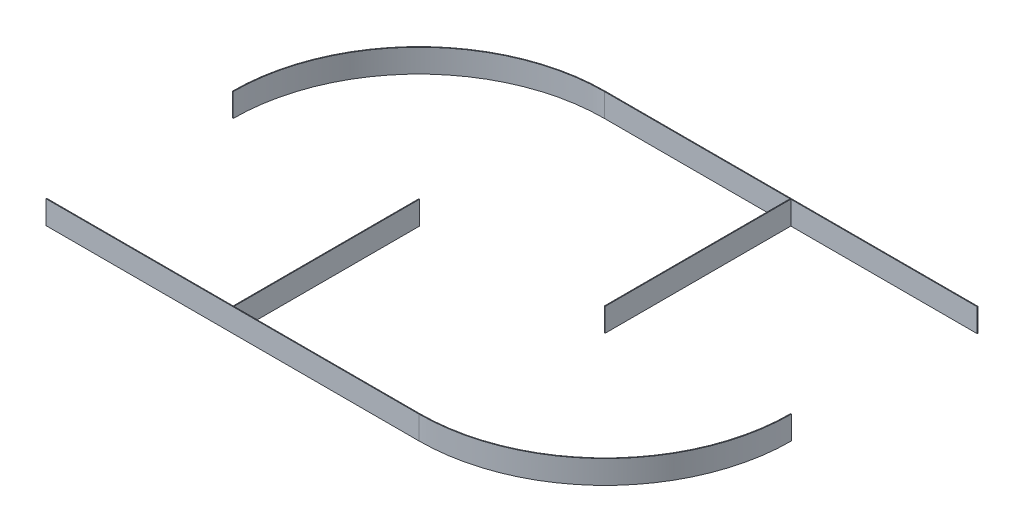
SolidWorks part; units mm, degrees
ref_plane "Front Plane" through (0, 0, 0) normal (0, 0, 1) x (1, 0, 0)
ref_plane "Top Plane" through (0, 0, 0) normal (0, 1, 0) x (1, 0, 0)
ref_plane "Right Plane" through (0, 0, 0) normal (1, 0, 0) x (0, 0, -1)
sketch "Sketch1" plane through (0, 0, 0) normal (0, 1, 0) x (1, 0, 0)
  line L0 (-304.8, 0) -> (304.8, 0) construction
  line L1 (304.8, -609.6) -> (-914.4, -609.6)
  line L2 (-304.8, 609.6) -> (914.4, 609.6)
  line L3 (304.8, 609.6) -> (304.8, 0)
  line L4 (-304.8, -609.6) -> (-304.8, 0)
  arc A0 (304.8, -609.6) -> (914.4, 0) centre (304.8, 0) ccw
  arc A1 (-304.8, 609.6) -> (-914.4, 0) centre (-304.8, 0) ccw
  point P4 (0, 0)
  dimension "D2" = 609.6
  dimension "D3" = 609.6
  dimension "D1" = 609.6
  dimension "D4" = 1219.2
  dimension "D5" = 1219.2
extrude "Extrude-Thin1" add sketch "Sketch1" along normal blind 76.2 thin thin type one direction wall 2.54
